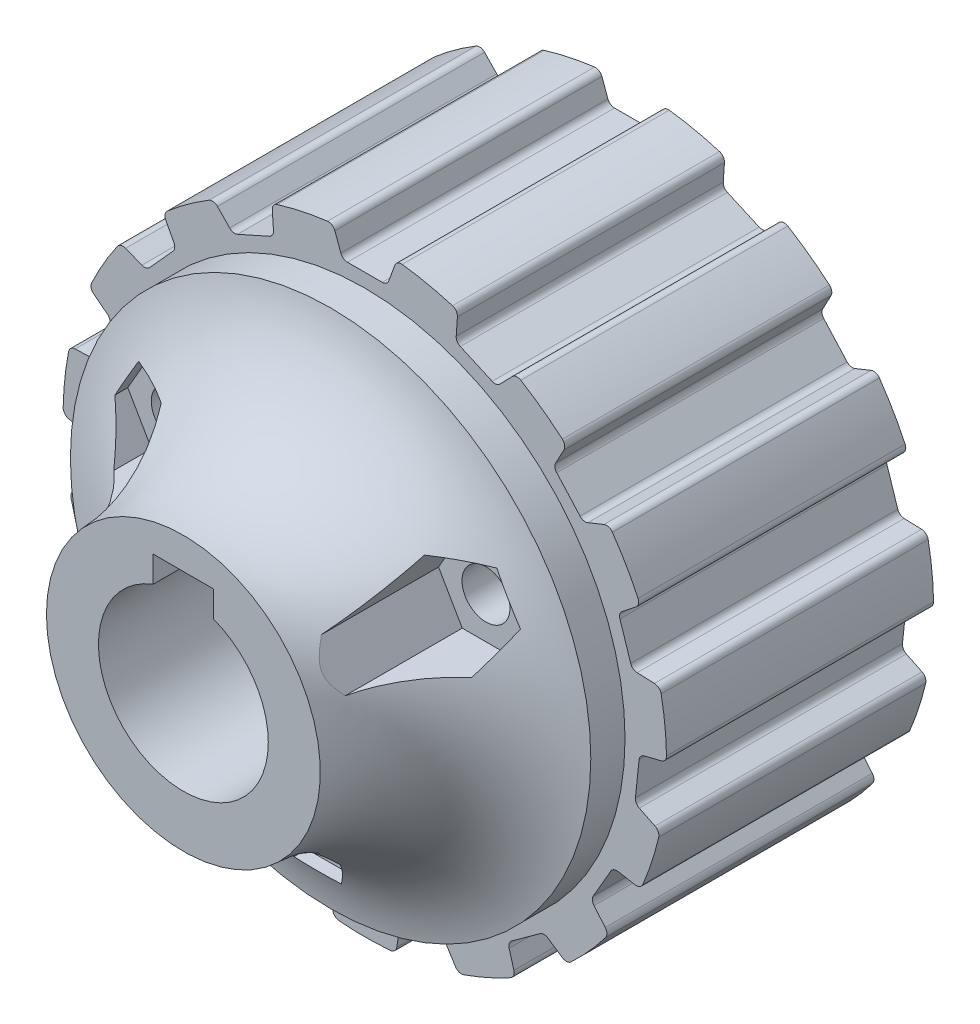
SolidWorks part; units mm, degrees
ref_plane "Front Plane" through (0, 0, 0) normal (0, 0, 1) x (1, 0, 0)
ref_plane "Top Plane" through (0, 0, 0) normal (0, 1, 0) x (1, 0, 0)
ref_plane "Right Plane" through (0, 0, 0) normal (1, 0, 0) x (0, 0, -1)
sketch "Sketch1" plane through (0, 0, 0) normal (0, 1, 0) x (1, 0, 0)
  line L0 (0, 36.1296) -> (0, -19.4741) construction
sketch "Sketch7" plane through (0, 0, 0) normal (0, 0, 1) x (1, 0, 0)
  line L0 (0, 0) -> (0, 20.9536) construction
  line L1 (-2.325, 21.9086) -> (-2.9401, 23.5986) construction
  line L2 (-2.325, 21.9086) -> (-1.6298, 19.9986) construction
  line L3 (-1.6298, 19.9986) -> (1.6298, 19.9986) construction
  line L4 (1.6298, 19.9986) -> (2.325, 21.9086) construction
  line L5 (2.325, 21.9086) -> (-2.325, 21.9086) construction
  line L6 (0, 19.9986) -> (0, 21.9086) construction
  line L7 (2.325, 21.9086) -> (2.9401, 23.5986) construction
  line L8 (-2.9401, 23.5986) -> (2.9401, 23.5986) construction
  line L9 (0, 0) -> (8.5226, 19.1421) construction
  line L10 (8.5226, 19.1421) -> (8.9611, 20.1269) construction
  line L11 (0, 21.9086) -> (0, 22.0316) construction
  line L12 (0, 22.0316) -> (0, 23.7811) construction
  line L13 (0, 22.9064) -> (9.3169, 20.926) construction
  line L14 (8.9611, 20.1269) -> (9.6726, 21.7251) construction
  circle A1 centre (0, 0) radius 20.9536 construction
  circle A2 centre (-1.2727, 20.5086) radius 0.51 construction
  circle A3 centre (1.2727, 20.5086) radius 0.51 construction
  circle A4 centre (0, 0) radius 22.0316
  circle A5 centre (0, 0) radius 23.7811 construction
  dimension "D3" = 40
  dimension "D6" = 1.02
  dimension "D1" = 3.6
  dimension "D2" = 24
  dimension "D7" = 9.525
  dimension "D4" = 1.91
  dimension "D5" = 4.65
extrude "Boss-Extrude1" add sketch "Sketch7" along normal blind 7.25 and the other way blind 7.25 contours A4 region at (0, 0, 0)
sketch "Sketch14" plane through (0, 0, 0) normal (1, 0, 0) x (0, 0, -1)
  line L0 (-18, 0) -> (-18, 10)
  line L1 (-18, 0) -> (0, 0)
  line L2 (0, 0) -> (0, 19)
  line L3 (0, 19) -> (-7.25, 19)
  line L4 (-7.25, 19) -> (-18, 10)
  line L5 (-7.25, 22.0316) -> (-7.25, -22.0316) construction
  line L6 (-18, 6.7395) -> (-3.3555, 19) construction
  arc A0 (-7.25, 19) -> (-18, 10) centre (-18.1316, 21.0773) cw
  dimension "D1" = 10
  dimension "D2" = 19
  dimension "D3" = 18
  dimension "D4" = 2.5
revolve "Revolve1" add sketch "Sketch14" angle 360 about L0 region at (0, 7.5733, 7.5341) region at (0, 9.2725, 16.1663) region at (0, 17.2765, 6.6188)
sketch "Sketch9" plane through (0, 0, 0) normal (0, 0, 1) x (1, 0, 0)
  line L0 (2, 0) -> (-2, 0) construction
  line L1 (-2, 0) -> (-2, 7.5) construction
  line L2 (-2, 7.5) -> (2, 7.5) construction
  line L3 (2, 7.5) -> (2, 0) construction
  circle A0 centre (0, 0) radius 6 construction
  dimension "D1" = 12
  dimension "D2" = 4
  dimension "D3" = 7.5
sketch "Sketch10" plane through (0, 0, 0) normal (0, 0, 1) x (1, 0, 0)
  line L0 (2, 0) -> (-2, 0) construction
  line L1 (-2.2, 7.7) -> (2.2, 7.7)
  line L2 (-2.2, 7.7) -> (-2.2, 0)
  line L3 (-2.2, 0) -> (2.2, 0)
  line L4 (2.2, 7.7) -> (2.2, 0)
  line L5 (-2, 7.5) -> (2, 7.5) construction
  line L6 (2, 7.5) -> (2, 0) construction
  circle A0 centre (0, 0) radius 6.2
  circle A1 centre (0, 0) radius 6 construction
  dimension "D1" = 0.2
  dimension "D2" = 0.2
  dimension "D3" = 0.2
extrude "Cut-Extrude3" cut sketch "Sketch10" against normal through all both and the other way through all contours A0 L4 L1 L2 | L2 A0 L4 L3 | L4 A0 L2 L3 region at (0, 6.8793, 0) region at (0, 3.0348, 0) region at (0, -0.8613, 0)
sketch "Sketch11" plane through (0, 0, 0) normal (0, 1, 0) x (1, 0, 0)
  line L0 (22.0316, 7.25) -> (-22.0316, 7.25) construction
  line L1 (11, 7.25) -> (17.5, 7.25)
  line L2 (11, 7.25) -> (11, 4.75)
  line L3 (11, 4.75) -> (17.5, 4.75)
  line L4 (17.5, 7.25) -> (17.5, 4.75)
  line L5 (-22.0316, -7.25) -> (22.0316, -7.25) construction
  line L6 (11, -7.25) -> (17.5, -7.25)
  line L7 (11, -7.25) -> (11, -4.75)
  line L8 (11, -4.75) -> (17.5, -4.75)
  line L9 (17.5, -7.25) -> (17.5, -4.75)
  line L11 (11, 4.75) -> (11, -4.75) construction
  line L12 (17.5, -4.75) -> (17.5, 4.75) construction
  line L13 (6.2, 7.25) -> (-6.2, 7.25) construction
  line L14 (0, 7.25) -> (22.5, 7.25)
  line L15 (0, 7.25) -> (0, -7.25)
  line L16 (0, -7.25) -> (22.5, -7.25)
  line L17 (22.5, 7.25) -> (22.5, -7.25)
  line L18 (-6.2, -7.25) -> (6.2, -7.25) construction
  line L19 (6, 7.25) -> (6, -7.25) construction
  dimension "D1" = 22.5
  dimension "D2" = 6
  dimension "D3" = 5
  dimension "D4" = 5
  dimension "D5" = 2.5
revolve "Cut-Revolve1" [suppressed] cut sketch "Sketch11" angle 360 about L0
sketch "Sketch15" plane through (0, 0, -7.25) normal (0, 0, -1) x (-1, 0, 0)
  circle A0 centre (0, 0) radius 8.0081
  circle A1 centre (0, 0) radius 2.25
  dimension "D1" = 4.5
extrude "Boss-Extrude2" add sketch "Sketch15" against normal blind 5.5
sketch "Sketch16" plane through (0, 0, -7.25) normal (0, 0, -1) x (-1, 0, 0)
  circle A0 centre (0, 0) radius 5
  dimension "D1" = 10
extrude "Cut-Extrude4" cut sketch "Sketch16" against normal blind 3
sketch "Sketch17" plane through (0, 0, -7.25) normal (0, 0, -1) x (-1, 0, 0)
  circle A0 centre (0, 0) radius 22.0316
  circle A1 centre (0, 0) radius 22.0316 construction
  circle A2 centre (0, 0) radius 5
  circle A3 centre (0, 0) radius 5 construction
extrude "Boss-Extrude3" add sketch "Sketch17" along normal blind 7.5
sketch "Sketch8" plane through (0, 0, 0) normal (0, 0, 1) x (1, 0, 0)
  line L6 (-1.6298, 19.9986) -> (-2.3698, 22.0316)
  line L7 (-2.3698, 22.0316) -> (2.3698, 22.0316)
  line L8 (2.3698, 22.0316) -> (1.6298, 19.9986)
  line L9 (1.6298, 19.9986) -> (-1.6298, 19.9986)
  line L10 (-2.325, 21.9086) -> (-1.6298, 19.9986) construction
  line L11 (1.6298, 19.9986) -> (2.325, 21.9086) construction
  line L12 (6.6453, 18.9326) -> (6.7962, 21.0908)
  line L13 (6.7962, 21.0908) -> (11.126, 19.163)
  line L14 (11.126, 19.163) -> (9.6231, 17.6067)
  line L15 (9.6231, 17.6067) -> (6.6453, 18.9326)
  line L16 (13.7713, 14.5929) -> (14.787, 16.5031)
  line L17 (14.787, 16.5031) -> (17.9584, 12.981)
  line L18 (17.9584, 12.981) -> (15.9524, 12.1705)
  line L19 (15.9524, 12.1705) -> (13.7713, 14.5929)
  line L20 (18.5162, 7.73) -> (20.221, 9.0619)
  line L21 (20.221, 9.0619) -> (21.6856, 4.5544)
  line L22 (21.6856, 4.5544) -> (19.5235, 4.6299)
  line L23 (19.5235, 4.6299) -> (18.5162, 7.73)
  line L24 (20.0594, -0.4695) -> (22.1587, 0.0539)
  line L25 (22.1587, 0.0539) -> (21.6632, -4.6597)
  line L26 (21.6632, -4.6597) -> (19.7187, -3.7113)
  line L27 (19.7187, -3.7113) -> (20.0594, -0.4695)
  line L28 (18.1342, -8.5879) -> (20.2649, -8.9635)
  line L29 (20.2649, -8.9635) -> (17.8951, -13.0681)
  line L30 (17.8951, -13.0681) -> (16.5044, -11.4108)
  line L31 (16.5044, -11.4108) -> (18.1342, -8.5879)
  line L32 (13.0734, -15.2212) -> (14.8671, -16.4311)
  line L33 (14.8671, -16.4311) -> (11.0327, -19.2169)
  line L34 (11.0327, -19.2169) -> (10.4363, -17.1372)
  line L35 (10.4363, -17.1372) -> (13.0734, -15.2212)
  line L36 (5.7521, -19.2227) -> (6.8986, -21.0575)
  line L37 (6.8986, -21.0575) -> (2.2626, -22.0429)
  line L38 (2.2626, -22.0429) -> (2.5637, -19.9005)
  line L39 (2.5637, -19.9005) -> (5.7521, -19.2227)
  line L40 (-2.5637, -19.9005) -> (-2.2626, -22.0429)
  line L41 (-2.2626, -22.0429) -> (-6.8986, -21.0575)
  line L42 (-6.8986, -21.0575) -> (-5.7521, -19.2227)
  line L43 (-5.7521, -19.2227) -> (-2.5637, -19.9005)
  line L44 (-10.4363, -17.1372) -> (-11.0327, -19.2169)
  line L45 (-11.0327, -19.2169) -> (-14.8671, -16.4311)
  line L46 (-14.8671, -16.4311) -> (-13.0734, -15.2212)
  line L47 (-13.0734, -15.2212) -> (-10.4363, -17.1372)
  line L48 (-16.5044, -11.4108) -> (-17.8951, -13.0681)
  line L49 (-17.8951, -13.0681) -> (-20.2649, -8.9635)
  line L50 (-20.2649, -8.9635) -> (-18.1342, -8.5879)
  line L51 (-18.1342, -8.5879) -> (-16.5044, -11.4108)
  line L52 (-19.7187, -3.7113) -> (-21.6632, -4.6597)
  line L53 (-21.6632, -4.6597) -> (-22.1587, 0.0539)
  line L54 (-22.1587, 0.0539) -> (-20.0594, -0.4695)
  line L55 (-20.0594, -0.4695) -> (-19.7187, -3.7113)
  line L56 (-19.5235, 4.6299) -> (-21.6856, 4.5544)
  line L57 (-21.6856, 4.5544) -> (-20.221, 9.0619)
  line L58 (-20.221, 9.0619) -> (-18.5162, 7.73)
  line L59 (-18.5162, 7.73) -> (-19.5235, 4.6299)
  line L60 (-15.9524, 12.1705) -> (-17.9584, 12.981)
  line L61 (-17.9584, 12.981) -> (-14.787, 16.5031)
  line L62 (-14.787, 16.5031) -> (-13.7713, 14.5929)
  line L63 (-13.7713, 14.5929) -> (-15.9524, 12.1705)
  line L64 (-9.6231, 17.6067) -> (-11.126, 19.163)
  line L65 (-11.126, 19.163) -> (-6.7962, 21.0908)
  line L66 (-6.7962, 21.0908) -> (-6.6453, 18.9326)
  line L67 (-6.6453, 18.9326) -> (-9.6231, 17.6067)
  circle A0 centre (0, 0) radius 22.0316 construction
  point P119 (0, 0)
  dimension "D1" = 15
extrude "Cut-Extrude2" cut sketch "Sketch8" against normal through all both and the other way through all
fillet "Fillet2" radius 0.51 60 edges at (-6.787, 20.9602, -3.75) (-11.035, 19.0689, -3.75) (-14.7256, 16.3875, -3.75) (-17.837, 12.9319, -3.75) (-20.1179, 8.9813, -3.75) (-21.5548, 4.5589, -3.75) (-22.0316, 0.0222, -3.75) (-21.5456, -4.6023, -3.75) (-20.1359, -8.9408, -3.75) (-17.8109, -12.9678, -3.75) (-14.7585, -16.3578, -3.75) (-10.9966, -19.0911, -3.75) (-6.8293, -20.9465, -3.75) (-2.2809, -21.9133, -3.75) (2.2809, -21.9133, -3.75) (6.8293, -20.9465, -3.75) (10.9966, -19.0911, -3.75) (14.7585, -16.3578, -3.75) (17.8109, -12.9678, -3.75) (20.1359, -8.9408, -3.75) (21.5456, -4.6023, -3.75) (22.0316, 0.0222, -3.75) (21.5548, 4.5589, -3.75) (20.1179, 8.9813, -3.75) (17.837, 12.9319, -3.75) (14.7256, 16.3875, -3.75) (11.035, 19.0689, -3.75) (6.787, 20.9602, -3.75) (2.325, 21.9086, -3.75) (-6.6453, 18.9326, -3.75) (-9.6231, 17.6067, -3.75) (-13.7713, 14.5929, -3.75) (-15.9524, 12.1705, -3.75) (-18.5162, 7.73, -3.75) (-19.5235, 4.6299, -3.75) (-20.0594, -0.4695, -3.75) (-19.7187, -3.7113, -3.75) (-18.1342, -8.5879, -3.75) (-16.5044, -11.4108, -3.75) (-13.0734, -15.2212, -3.75) (-10.4363, -17.1372, -3.75) (-5.7521, -19.2227, -3.75) (-2.5637, -19.9005, -3.75) (2.5637, -19.9005, -3.75) (5.7521, -19.2227, -3.75) (10.4363, -17.1372, -3.75) (13.0734, -15.2212, -3.75) (16.5044, -11.4108, -3.75) (18.1342, -8.5879, -3.75) (19.7187, -3.7113, -3.75) (20.0594, -0.4695, -3.75) (19.5235, 4.6299, -3.75) (18.5162, 7.73, -3.75) (15.9524, 12.1705, -3.75) (13.7713, 14.5929, -3.75) (9.6231, 17.6067, -3.75) (6.6453, 18.9326, -3.75) (1.6298, 19.9986, -3.75) (-1.6298, 19.9986, -3.75) (-2.325, 21.9086, -3.75)
sketch "Sketch18" plane through (0, 0, -14.75) normal (0, 0, -1) x (-1, 0, 0)
  circle A0 centre (0, 0) radius 5
  circle A1 centre (0, 0) radius 27.0316
  circle A2 centre (0, 0) radius 22.0316
  circle A3 centre (0, 0) radius 5 construction
  arc A4 (-2.7297, 21.8619) -> (-6.3983, 21.0821) centre (0, 0) ccw construction
  dimension "D1" = 5
extrude "Boss-Extrude4" add sketch "Sketch18" along normal blind 2.5 contours A1 A2 | A2 A0 region at (26.2671, 0, -14.75) region at (21.4085, 0, -14.75)
sketch "Sketch19" plane through (0, 0, 7.25) normal (0, 0, 1) x (1, 0, 0)
  circle A0 centre (0, 0) radius 19
  circle A1 centre (0, 0) radius 27.0316
  circle A2 centre (0, 0) radius 27.0316 construction
  circle A3 centre (0, 0) radius 19 construction
extrude "Boss-Extrude5" add sketch "Sketch19" against normal blind 2.5
fillet "Fillet3" [suppressed] radius 0.5
sketch "Sketch20" plane through (0, 0, 18) normal (0, 0, 1) x (1, 0, 0)
  line L0 (-2.2, 5.7966) -> (-2.2, 7.7)
  line L1 (-2.2, 7.7) -> (2.2, 7.7)
  line L2 (-2.2, 7.7) -> (2.2, 7.7) construction
  line L3 (2.2, 7.7) -> (2.2, 5.7966)
  circle A0 centre (0, 0) radius 6.2
  arc A1 (-2.2, 5.7966) -> (2.2, 5.7966) centre (0, 0) ccw construction
  arc M2 (2.2, 5.7966) -> (-2.2, 5.7966) centre (0, 0) cw
  line M3 (-2.2, 5.7966) -> (-2.2, 7.7)
  line M4 (-2.2, 7.7) -> (2.2, 7.7)
  line M5 (2.2, 7.7) -> (2.2, 5.7966)
extrude "Cut-Extrude5" cut sketch "Sketch20" against normal through all contours A0 M5 M4 M3 | A0 M2 region at (0, 6.8793, 18) region at (0, 0, 18)
ref_plane "Plane1" through (0, 0, -5.25) normal (0, 0, 1) x (1, 0, 0)
sketch "Sketch21" plane through (0, 0, -5.25) normal (0, 0, 1) x (1, 0, 0)
  circle A0 centre (0, 0) radius 8.0081
  circle A1 centre (0, 0) radius 2.25
  circle A2 centre (0, 0) radius 6.2
  arc A3 (-2.2, 5.7966) -> (2.2, 5.7966) centre (0, 0) ccw construction
  dimension "D1" = 4.5
extrude "Boss-Extrude6" add sketch "Sketch21" against normal blind 2.5 contours A2 A1 | A0 A2 region at (-7.7816, 0, -5.25) region at (-6.0246, 0, -5.25)
extrude "Boss-Extrude7" add sketch "Sketch21<4>" against normal up to surface (12 mm away) contours A0 A2 region at (-7.7816, 0, -5.25) up to face at (0, 3.7491, -17.25)
sketch "Sketch21<4>" plane through (0, 0, -5.25) normal (0, 0, 1) x (1, 0, 0) same geometry as "Sketch21"
sketch "Sketch22" plane through (0, 0, 0) normal (0, 1, 0) x (1, 0, 0)
  line L0 (-27.0316, 17.25) -> (-27.0316, 14.75) construction
  line L1 (-27.0316, 17.25) -> (27.0316, 17.25)
  line L2 (-27.0316, 17.25) -> (-27.0316, 14.75)
  line L3 (-27.0316, 14.75) -> (27.0316, 14.75)
  line L4 (27.0316, 17.25) -> (27.0316, 14.75)
  line L5 (-27.0316, 17.25) -> (27.0316, 14.75) construction
  line L6 (-27.0316, 14.75) -> (27.0316, 17.25) construction
  line L7 (-10, -18) -> (10, -18) construction
  line L8 (-27.0316, 14.75) -> (27.0316, 14.75)
  line L9 (-27.0316, 14.75) -> (-27.0316, -18)
  line L10 (-27.0316, -18) -> (27.0316, -18)
  line L11 (27.0316, 14.75) -> (27.0316, -18)
  point P0 (0, 16)
extrude "Cut-Extrude6" cut sketch "Sketch22" against normal through all both and the other way through all contours L4 L1 L2 L3 region at (0, 0, -16)
sketch "Sketch23" plane through (0, 0, -14.75) normal (0, 0, -1) x (-1, 0, 0)
  line L0 (0, 19.9986) -> (0, 6.2) construction
  line L1 (1.2727, 19.9986) -> (-1.2727, 19.9986) construction
  circle A0 centre (0, 0) radius 13.0993 construction
  circle A1 centre (0, 0) radius 6.2 construction
  circle A2 centre (0, -13.0993) radius 1.75
  circle A3 centre (-11.3443, 6.5497) radius 1.75
  circle A4 centre (11.3443, 6.5497) radius 1.75
  point P10 (0, 13.0993)
  point P19 (0, 0)
  point P26 (0, 0)
  dimension "D1" = 3.5
  dimension "D2" = 3
extrude "Cut-Extrude7" cut sketch "Sketch23" against normal blind 6
ref_plane "Plane2" through (0, 0, -12.25) normal (0, 0, -1) x (-1, 0, 0)
sketch "Sketch24" plane through (0, 0, -12.25) normal (0, 0, -1) x (-1, 0, 0)
  line L0 (-19.08, 11.0158) -> (-14.3443, 8.2817) construction
  line L1 (-11.3443, 3.0856) -> (-8.3443, 4.8176)
  line L2 (-8.3443, 4.8176) -> (-8.3443, 8.2817)
  line L3 (-8.3443, 8.2817) -> (-11.3443, 10.0138)
  line L4 (-11.3443, 10.0138) -> (-14.3443, 8.2817)
  line L5 (-14.3443, 8.2817) -> (-14.3443, 4.8176)
  line L6 (-14.3443, 4.8176) -> (-11.3443, 3.0856)
  line L7 (3, -14.8314) -> (3, -11.3673)
  line L8 (3, -11.3673) -> (0, -9.6352)
  line L9 (0, -9.6352) -> (-3, -11.3673)
  line L10 (-3, -11.3673) -> (-3, -14.8314)
  line L11 (-3, -14.8314) -> (0, -16.5634)
  line L12 (0, -16.5634) -> (3, -14.8314)
  line L13 (11.3443, 3.0856) -> (14.3443, 4.8176)
  line L14 (14.3443, 4.8176) -> (14.3443, 8.2817)
  line L15 (14.3443, 8.2817) -> (11.3443, 10.0138)
  line L16 (11.3443, 10.0138) -> (8.3443, 8.2817)
  line L17 (8.3443, 8.2817) -> (8.3443, 4.8176)
  line L18 (8.3443, 4.8176) -> (11.3443, 3.0856)
  line L19 (-11.3443, 6.5497) -> (-14.3443, 8.2817) construction
  line L20 (11.3443, 6.5497) -> (14.3443, 8.2817) construction
  line L21 (19.08, 11.0158) -> (14.3443, 8.2817) construction
  line L22 (0, -22.0316) -> (0, -16.5634) construction
  circle A0 centre (-11.3443, 6.5497) radius 3 construction
  circle A1 centre (0, -13.0993) radius 3 construction
  circle A2 centre (11.3443, 6.5497) radius 3 construction
  arc A3 (-18.0731, 12.5999) -> (-19.9484, 9.3518) centre (0, 0) ccw construction
  arc A5 (19.9484, 9.3518) -> (18.0731, 12.5999) centre (0, 0) ccw construction
  arc A6 (-1.8753, -21.9517) -> (1.8753, -21.9517) centre (0, 0) ccw construction
  dimension "D1" = 6
extrude "Cut-Extrude8" cut sketch "Sketch24" against normal blind 3
sketch "Sketch25" plane through (0, 0, -9.25) normal (0, 0, -1) x (-1, 0, 0)
  circle A0 centre (0, -13.0993) radius 1.75
  circle A1 centre (-11.3443, 6.5497) radius 1.75
  circle A2 centre (11.3443, 6.5497) radius 1.75
  circle A4 centre (0, -13.0993) radius 1.75 construction
extrude "Boss-Extrude8" add sketch "Sketch25" against normal blind 0.2
sketch "Sketch26" plane through (0, 0, 4.75) normal (0, 0, -1) x (-1, 0, 0)
  circle A0 centre (11.3443, 6.5497) radius 1.75
  circle A1 centre (0, 0) radius 6.2
  circle A2 centre (0, -13.0993) radius 1.75
  circle A3 centre (-11.3443, 6.5497) radius 1.75
  circle A4 centre (0, 0) radius 17.5
  circle A5 centre (0, -13.0993) radius 1.75 construction
  circle A6 centre (11.3443, 6.5497) radius 1.75 construction
  circle A7 centre (-11.3443, 6.5497) radius 1.75 construction
  circle A8 centre (0, 0) radius 6.2 construction
  dimension "D1" = 35
extrude "Boss-Extrude9" add sketch "Sketch26" along normal up to surface (19.5 mm away) up to face at (-1.75, -13.0993, -14.75)
extrude "Cut-Extrude9" cut sketch "Sketch26<2>" against normal through all both and the other way through all contours A2 | A0 | A3 region at (-11.3443, 6.5497, 4.75) region at (0, -13.0993, 4.75) region at (11.3443, 6.5497, 4.75)
sketch "Sketch26<2>" plane through (0, 0, 4.75) normal (0, 0, -1) x (-1, 0, 0) same geometry as "Sketch26"
sketch "Sketch28" plane through (0, 0, 7.25) normal (0, 0, 1) x (1, 0, 0)
  line L1 (-1.7321, -10.0993) -> (-3.4641, -13.0993)
  line L2 (-3.4641, -13.0993) -> (-1.7321, -16.0993)
  line L3 (-1.7321, -16.0993) -> (1.7321, -16.0993)
  line L4 (1.7321, -16.0993) -> (3.4641, -13.0993)
  line L5 (3.4641, -13.0993) -> (1.7321, -10.0993)
  line L6 (1.7321, -10.0993) -> (-1.7321, -10.0993)
  line L7 (-13.0764, 9.5497) -> (-14.8084, 6.5497)
  line L8 (-14.8084, 6.5497) -> (-13.0764, 3.5497)
  line L9 (-13.0764, 3.5497) -> (-9.6123, 3.5497)
  line L10 (-9.6123, 3.5497) -> (-7.8802, 6.5497)
  line L11 (-7.8802, 6.5497) -> (-9.6123, 9.5497)
  line L12 (-9.6123, 9.5497) -> (-13.0764, 9.5497)
  line L13 (9.6123, 9.5497) -> (7.8802, 6.5497)
  line L14 (7.8802, 6.5497) -> (9.6123, 3.5497)
  line L15 (9.6123, 3.5497) -> (13.0764, 3.5497)
  line L16 (13.0764, 3.5497) -> (14.8084, 6.5497)
  line L17 (14.8084, 6.5497) -> (13.0764, 9.5497)
  line L18 (13.0764, 9.5497) -> (9.6123, 9.5497)
  circle A0 centre (0, -13.0993) radius 3 construction
  circle A1 centre (-11.3443, 6.5497) radius 3 construction
  circle A2 centre (11.3443, 6.5497) radius 3 construction
  circle A3 centre (0, 0) radius 10.0993 construction
  dimension "D1" = 6
  dimension "D2" = 6
  dimension "D3" = 6
extrude "Cut-Extrude10" cut sketch "Sketch28" along normal through all
sketch "Sketch29" plane through (0, 0, 7.25) normal (0, 0, 1) x (1, 0, 0)
  circle A0 centre (0, 0) radius 27.0316
  circle A1 centre (0, 0) radius 19
  circle A2 centre (0, 0) radius 19 construction
  circle A3 centre (0, 0) radius 27.0316 construction
extrude "Cut-Extrude11" cut sketch "Sketch29" against normal up to surface (2.5 mm away) up to face at (27.0316, 0, 4.75)
